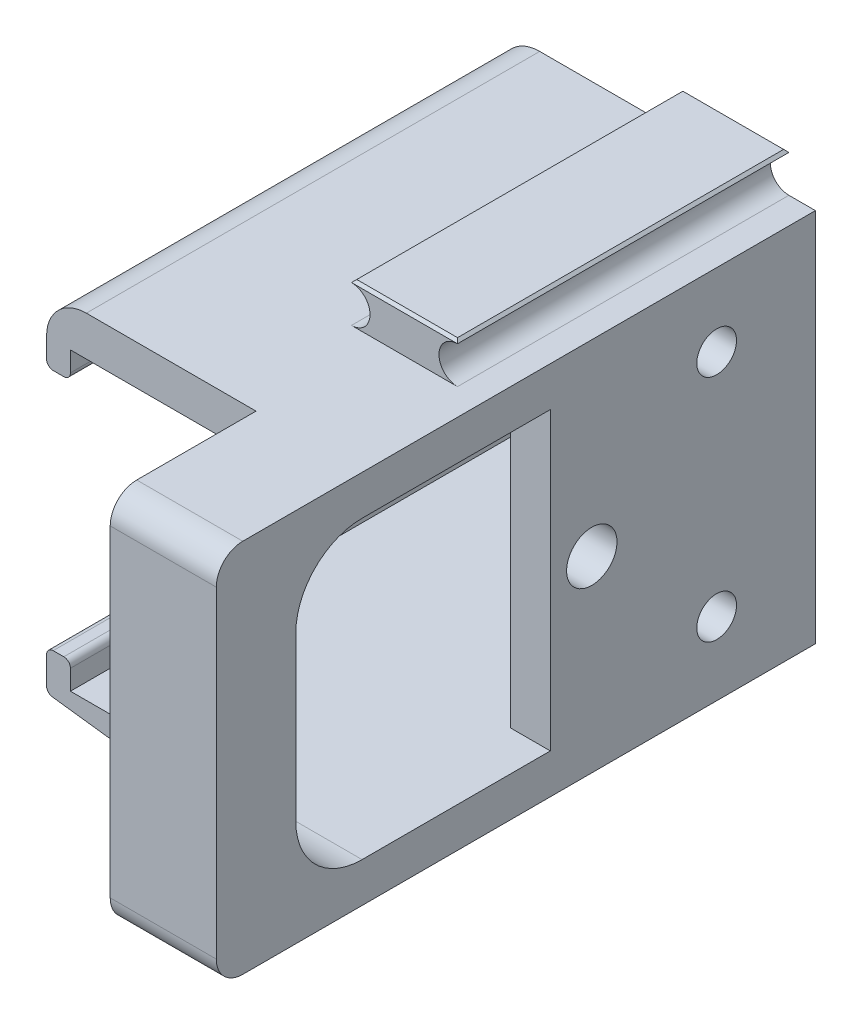
SolidWorks part; units mm, degrees
ref_plane "Front Plane" through (0, 0, 0) normal (0, 0, 1) x (1, 0, 0)
ref_plane "Top Plane" through (0, 0, 0) normal (0, 1, 0) x (1, 0, 0)
ref_plane "Right Plane" through (0, 0, 0) normal (1, 0, 0) x (0, 0, -1)
sketch "U" plane through (0, 0, 0) normal (1, 0, 0) x (0, 0, -1)
  line L0 (12, 20.3) -> (12, 23.3)
  line L1 (12, -2) -> (-22.2, -2)
  line L3 (12, 20.3) -> (-22.2, 20.3)
  line L4 (-27.2, 3) -> (-27.2, 15.3)
  line L5 (12, 23.3) -> (-31.2, 23.3)
  line L6 (-33.2, 21.3) -> (-33.2, -3)
  line L7 (-31.2, -5) -> (12, -5)
  line L8 (12, -5) -> (12, -2)
  arc A0 (-31.2, -5) -> (-33.2, -3) centre (-31.2, -3) cw
  arc A1 (-31.2, 23.3) -> (-33.2, 21.3) centre (-31.2, 21.3) ccw
  arc A2 (-27.2, 3) -> (-22.2, -2) centre (-22.2, 3) ccw
  arc A3 (-27.2, 15.3) -> (-22.2, 20.3) centre (-22.2, 15.3) cw
  point P15 (-27.2, -2)
  point P18 (-27.2, 20.3)
  dimension "D5" = 2
  dimension "D6" = 5
  dimension "D1" = 39.2
  dimension "D2" = 22.3
  dimension "D3" = 3
  dimension "D4" = 6
  dimension "D7" = 43.2
  dimension "D8" = 43.2
  dimension "D9" = 3
extrude "Boss-Extrude1" add sketch "U" against normal blind 5 and the other way blind 3
ref_plane "Plano1" through (0, 9.15, 0) normal (0, 1, 0) x (1, 0, 0)
sketch "Sketch2" plane through (0, 0, 0) normal (1, 0, 0) x (0, 0, -1)
  line L0 (12, 23.3) -> (-31.2, 23.3) construction
  line L1 (12, -5) -> (-8, -5)
  line L2 (12, -5) -> (12, 23.3)
  line L3 (12, 23.3) -> (-8, 23.3)
  line L4 (-8, -5) -> (-8, 23.3)
  line L5 (-4.87, 23.3) -> (-4.87, -5) construction
  circle A0 centre (-4.87, 9.15) radius 1.9
  point P11 (0, 0)
  point P12 (-4.87, 9.15)
  dimension "D2" = 16.87
  dimension "D3" = 3.8
  dimension "D1" = 20
extrude "Boss-Extrude2" add sketch "Sketch2" along normal blind 3
sketch "AgujerosMotor" plane through (3, 0, 0) normal (1, 0, 0) x (0, 0, -1)
  line L0 (4.55, 20.3) -> (4.55, -2) construction
  line L1 (2, 20.3) -> (10, 20.3) construction
  line L2 (2, 20.3) -> (2, -2) construction
  line L3 (2, -2) -> (10, -2) construction
  line L4 (10, 20.3) -> (10, -2) construction
  line L5 (4.55, 9.15) -> (10, 9.15) construction
  line L7 (10, -2) -> (10, 20.3) construction
  line L9 (12, -2) -> (-8, -2) construction
  circle A0 centre (4.55, 0.5) radius 1.5
  circle A1 centre (4.55, 17.8) radius 1.5
  dimension "D2" = 3
  dimension "D4" = 17.3
  dimension "D1" = 5.45
  dimension "D3" = 2.5
extrude "Cut-Extrude1" cut sketch "AgujerosMotor" against normal up to next
sketch "Sketch5" plane through (-5, 0, 0) normal (-1, 0, 0) x (0, 0, 1)
  line L0 (22.2, 20.3) -> (-12, 20.3) construction
  line L5 (-12, 23.3) -> (22.2, 23.3)
  line L6 (-12, 23.3) -> (-12, 20.3)
  line L7 (-12, 20.3) -> (22.2, 20.3)
  line L8 (22.2, 23.3) -> (22.2, 20.3)
  arc A0 (27.2, 15.3) -> (22.2, 20.3) centre (22.2, 15.3) ccw construction
  dimension "D1" = 3
extrude "Boss-Extrude3" add sketch "Sketch5" along normal blind 15.8
sketch "Croquis1" plane through (0, 20.3, 0) normal (0, -1, 0) x (1, 0, 0)
  line L0 (-20.8, 22.2) -> (-5, 22.2) construction
  line L1 (-20.8, -12) -> (-19, -12)
  line L2 (-20.8, -12) -> (-20.8, 22.2)
  line L3 (-20.8, 22.2) -> (-19, 22.2)
  line L4 (-19, -12) -> (-19, 22.2)
  dimension "D1" = 1.8
extrude "Saliente-Extruir1" add sketch "Croquis1" along normal blind 2
sketch "Croquis3" plane through (0, 23.3, 0) normal (0, 1, 0) x (1, 0, 0)
  line L1 (-7, -13) -> (1, -13)
  line L2 (-7, -13) -> (-7, 12)
  line L3 (-7, 12) -> (1, 12)
  line L4 (1, -13) -> (1, 12)
  line L5 (3, 12) -> (-20.8, 12) construction
  line L6 (3, 12) -> (3, -31.2) construction
  dimension "D1" = 25
  dimension "D2" = 8
  dimension "D3" = 2
extrude "Saliente-Extruir2" add sketch "Croquis3" along normal blind 3
chamfer "Chaflán2" distance 0.2 4 edges at (-3, 26.3, -12) (-7, 26.3, 0.5) (-3, 26.3, 13) (1, 26.3, 0.5)
sketch "Croquis7" plane through (0, 0, 13) normal (0, 0, 1) x (1, 0, 0)
  line L0 (-7, 23.3) -> (1, 23.3) construction
  line L1 (1, 26.1) -> (1, 23.3) construction
  line L2 (1, 26.1) -> (1, 23.3)
  line L3 (-7, 23.3) -> (-7, 26.1)
  arc A0 (1, 26.1) -> (1, 23.3) centre (1, 24.7) ccw
  arc A1 (-7, 23.3) -> (-7, 26.1) centre (-7, 24.7) ccw construction
  arc A2 (-7, 23.3) -> (-7, 26.1) centre (-7, 24.7) ccw
extrude "Cortar-Extruir1" cut sketch "Croquis7" against normal through all
mirror "Simetría11" about plane through (0, 9.15, 0) normal (0, 1, 0) of "Boss-Extrude3"
chamfer "Chaflán3" distance 2 distance2 15.8 1 edges at (-20.8, -5, 5.1) first distance on face at (-20.8, -3.5, 5.1)
mirror "Simetría14" about plane through (0, 9.15, 0) normal (0, 1, 0) of "Saliente-Extruir1"
fillet "Redondeo3" radius 0.5 3 edges at (-20.8, -3, 5.1) (-19, 0, 5.1) (-20.8, 0, 5.1)
fillet "Redondeo4" radius 0.5 2 edges at (-19, 18.3, 5.1) (-20.8, 18.3, 5.1)
fillet "Redondeo5" radius 3 1 edges at (-20.8, 23.3, 5.1)
